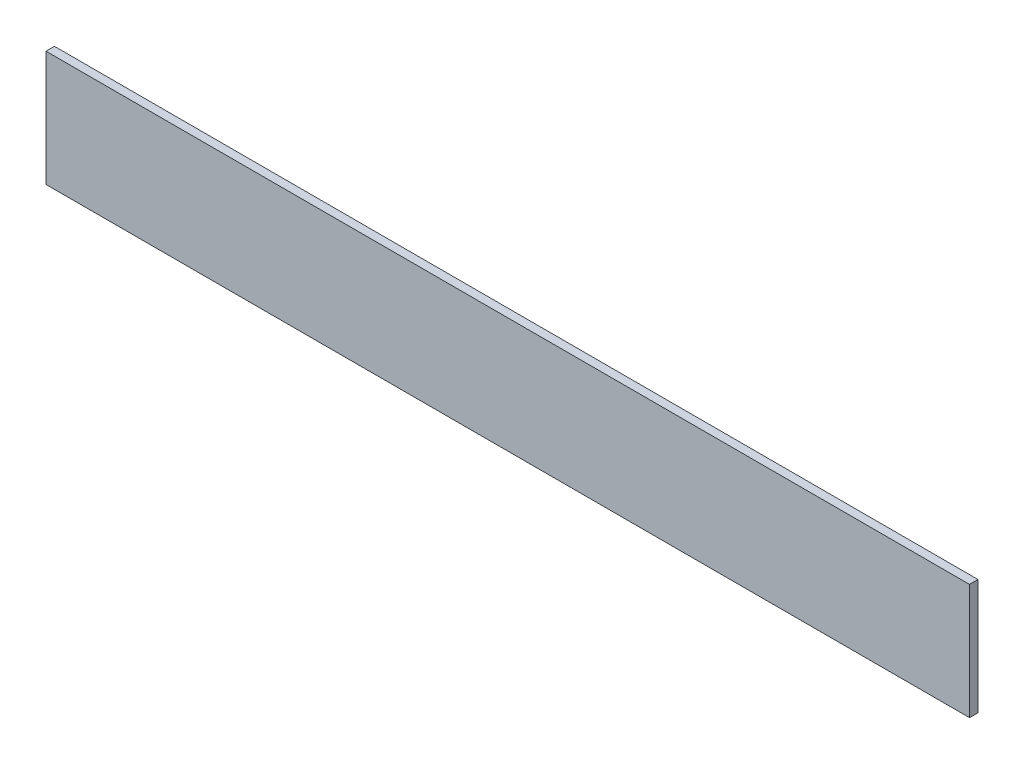
SolidWorks part; units mm, degrees
ref_plane "Front Plane" through (0, 0, 0) normal (0, 0, 1) x (1, 0, 0)
ref_plane "Top Plane" through (0, 0, 0) normal (0, 1, 0) x (1, 0, 0)
ref_plane "Right Plane" through (0, 0, 0) normal (1, 0, 0) x (0, 0, -1)
sketch "Sketch1" plane through (0, 0, 0) normal (0, 0, 1) x (1, 0, 0)
  line L1 (-82.55, 57.15) -> (527.05, 57.15)
  line L2 (-82.55, 57.15) -> (-82.55, -19.05)
  line L3 (-82.55, -19.05) -> (527.05, -19.05)
  line L4 (527.05, 57.15) -> (527.05, -19.05)
  dimension "D1" = 76.2
  dimension "D2" = 609.6
extrude "Boss-Extrude1" add sketch "Sketch1" along normal blind 5.588
equation "\"width\"= 9in"
equation "\"Height\"= 18in"
equation "\"thick\"= 0.22"
equation "\"D1@Boss-Extrude1\"=\"thick\""
